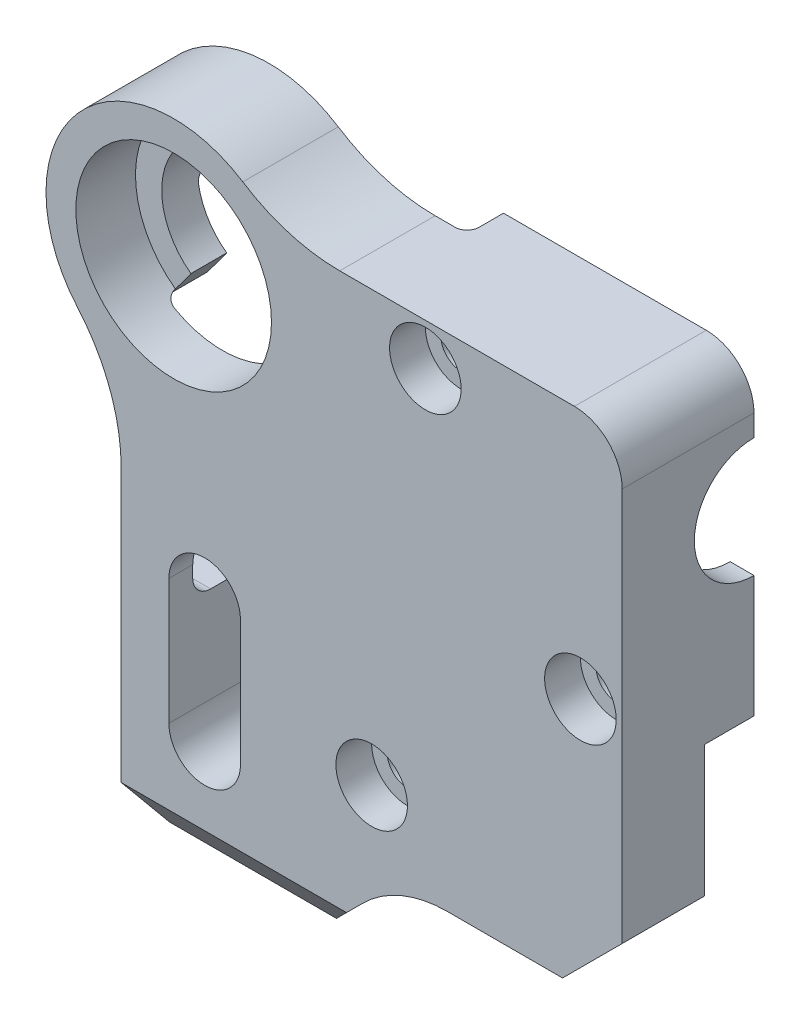
SolidWorks part; units mm, degrees
ref_plane "Plano frontal" through (0, 0, 0) normal (0, 0, 1) x (1, 0, 0)
ref_plane "Plano superior" through (0, 0, 0) normal (0, 1, 0) x (1, 0, 0)
ref_plane "Plano direito" through (0, 0, 0) normal (1, 0, 0) x (0, 0, -1)
sketch "Esboço1" plane through (0, 0, 0) normal (0, 0, 1) x (1, 0, 0)
  line L0 (0, 0) -> (-16.6, 14.4) construction
  line L1 (-21, -2.4562) -> (-21, -30.2)
  line L2 (-21, -30.2) -> (-7, -30.2)
  line L3 (-7, -30.2) -> (-0.7289, -23.9289)
  line L4 (6.3421, -21) -> (16, -21)
  line L5 (21, -16) -> (21, 17)
  line L6 (17, 21) -> (-2.6741, 21)
  line L7 (16, -21) -> (21, -16)
  line L8 (0, 0) -> (17.5, 0) construction
  line L9 (0, 0) -> (0, -15) construction
  line L10 (21, 10.2) -> (-37.1781, 10.2) construction
  line L11 (-14, -8.49) -> (-14, -19.01) construction
  line L12 (-11, -8.49) -> (-11, -19.01)
  line L13 (-17, -8.49) -> (-17, -19.01)
  arc A0 (-10.8021, 23.393) -> (-24.677, 7.3821) centre (-16.6, 14.4) ccw
  circle A1 centre (-16.6, 14.4) radius 8.2 construction
  arc A2 (21, 17) -> (17, 21) centre (17, 17) ccw
  arc A3 (-21, -2.4562) -> (-24.677, 7.3821) centre (-36, -2.4562) ccw
  arc A4 (-2.6741, 21) -> (-10.8021, 23.393) centre (-2.6741, 36) cw
  arc A5 (-0.7289, -23.9289) -> (6.3421, -21) centre (6.3421, -31) cw
  circle A7 centre (17.5, 0) radius 1.7
  circle A8 centre (0, -15) radius 1.7
  circle A9 centre (-16.6, 14.4) radius 4 construction
  circle A10 centre (4.5, 17.5) radius 1.7
  circle A11 centre (-16.6, 14.4) radius 2.7
  arc A12 (-11, -8.49) -> (-17, -8.49) centre (-14, -8.49) ccw
  arc A13 (-17, -19.01) -> (-11, -19.01) centre (-14, -19.01) ccw
  point P9 (21, -21)
  point P32 (-14, -13.75)
  dimension "D1" = 16.4
  dimension "D10" = 4
  dimension "D11" = 15
  dimension "D12" = 10
  dimension "D15" = 4
  dimension "D19" = 3.4
  dimension "D22" = 8
  dimension "D25" = 5.4
  dimension "D26" = 2.5
  dimension "D3" = 4.4
  dimension "D4" = 44.6
  dimension "D5" = 14
  dimension "D6" = 135
  dimension "D7" = 9.2
  dimension "D8" = 42
  dimension "D9" = 6.6
  dimension "D13" = 5
  dimension "D14" = 5
  dimension "D16" = 16.6
  dimension "D17" = 14.4
  dimension "D18" = 17.5
  dimension "D20" = 15
  dimension "D21" = 10.8
  dimension "D23" = 3.1
  dimension "D24" = 21.1
  dimension "D27" = 6
  dimension "D28" = 10.52
  dimension "D29" = 11.19
extrude "Ressalto-extrusão1" add sketch "Esboço1" along normal blind 14 contours L3 A5 L4 L7 L5 A2 L6 A4 A0 A3 L1 L2 A13 L13 A12 L12 A11 A10 A8 A7 region at (-1.918, -0.5242, 0)
sketch "Esboço2" plane through (0, 0, 14) normal (0, 0, -1) x (-1, 0, 0)
  circle A0 centre (-17.5, 0) radius 3
  circle A1 centre (0, -15) radius 3
  circle A2 centre (-4.5, 17.5) radius 3
  dimension "D1" = 6
extrude "Corte-extrusão1" cut sketch "Esboço2" along normal blind 3
sketch "Esboço3" plane through (-21, 0, 0) normal (-1, 0, 0) x (0, 0, 1)
  line L10 (14, -30.2) -> (14, -23.2)
  line L11 (14, -2.4562) -> (14, -30.2) construction
  line L12 (14, -23.2) -> (7, -30.2)
  line L13 (14, -30.2) -> (0, -30.2) construction
  line L14 (7, -30.2) -> (14, -30.2)
  dimension "D1" = 7
extrude "Corte-extrusão2" cut sketch "Esboço3" against normal through all
sketch "Esboço4" plane through (0, 0, 0) normal (0, 0, 1) x (1, 0, 0)
  line L10 (0, 11) -> (0, 21)
  line L22 (21, -16) -> (21, 17) construction
  line L24 (17, 21) -> (-2.6741, 21) construction
  line L25 (0, -11) -> (-11, -11)
  line L26 (-11, -8.49) -> (-11, -19.01) construction
  line L27 (-17, -8.49) -> (-17, -19.01) construction
  line L28 (-17, -8.49) -> (-17, -11)
  line L29 (-11, -8.49) -> (-11, -11)
  line L30 (-17, -11) -> (-21, -11)
  line L32 (-21, -23.2) -> (0.0843, -23.2)
  line L33 (6.3421, -21) -> (16, -21)
  line L34 (16, -21) -> (21, -16)
  line L35 (21, -16) -> (21, 17)
  line L36 (17, 21) -> (-2.6741, 21)
  line L37 (-21, -2.4562) -> (-21, -23.2)
  line L38 (-21, -23.2) -> (0.0843, -23.2)
  line L43 (0, 21) -> (-2.6741, 21)
  line L44 (-21, -2.4562) -> (-21, -11)
  circle A8 centre (0, 0) radius 5.5
  arc A9 (0, -11) -> (0, 11) centre (0, 0) ccw
  arc A19 (-11, -8.49) -> (-17, -8.49) centre (-14, -8.49) ccw construction
  arc A20 (-11, -8.49) -> (-17, -8.49) centre (-14, -8.49) ccw
  arc A24 (6.3421, -21) -> (0.0843, -23.2) centre (6.3421, -31) ccw
  arc A25 (21, 17) -> (17, 21) centre (17, 17) ccw
  arc A26 (-10.8021, 23.393) -> (-2.6741, 21) centre (-2.6741, 36) ccw
  arc A27 (-10.8021, 23.393) -> (-24.677, 7.3821) centre (-16.6, 14.4) ccw
  arc A28 (-21, -2.4562) -> (-24.677, 7.3821) centre (-36, -2.4562) ccw
  arc A31 (-10.8021, 23.393) -> (-2.6741, 21) centre (-2.6741, 36) ccw
  arc A32 (-10.8021, 23.393) -> (-24.677, 7.3821) centre (-16.6, 14.4) ccw
  arc A33 (-21, -2.4562) -> (-24.677, 7.3821) centre (-36, -2.4562) ccw
  line M87 (-11, -19.01) -> (-11, -8.49)
  arc M88 (-11, -8.49) -> (-17, -8.49) centre (-14, -8.49) ccw
  line M89 (-17, -8.49) -> (-17, -19.01)
  circle M90 centre (-16.6, 14.4) radius 2.7
  line M96 (-21, -30.2) -> (-21, -2.4562)
  arc M97 (-21, -2.4562) -> (-24.677, 7.3821) centre (-36, -2.4562) ccw
  arc M98 (-24.677, 7.3821) -> (-10.8021, 23.393) centre (-16.6, 14.4) cw
  arc M99 (-10.8021, 23.393) -> (-2.6741, 21) centre (-2.6741, 36) ccw
  line M100 (-2.6741, 21) -> (17, 21)
  dimension "D1" = 11
  dimension "D2" = 22
  dimension "D3" = 21
  dimension "D4" = 0
extrude "Corte-extrusão3" cut sketch "Esboço4" along normal blind 12 contours A9 L25 L30 L10 A8 M87 M88 M89 M96 M97 M98 M99 M100 M90 region at (-9.6685, 6.5214, 0)
sketch "Esboço5" plane through (0, 0, 0) normal (0, 0, 1) x (1, 0, 0)
  circle A1 centre (0, 0) radius 5.5
  circle A3 centre (0, 0) radius 5.5
  dimension "D1" = 0
extrude "Corte-extrusão4" cut sketch "Esboço5" along normal blind 5.55
sketch "Esboço6" plane through (0, 0, 5.55) normal (0, 0, -1) x (-1, 0, 0)
  circle A0 centre (0, 0) radius 4.3
  dimension "D1" = 8.6
extrude "Ressalto-extrusão2" add sketch "Esboço6" along normal blind 4
sketch "Esboço7" plane through (0, 0, 0) normal (0, 0, -1) x (-1, 0, 0)
  line L0 (-21, -5) -> (-9.798, -5)
  line L1 (-21, -16) -> (-21, 17) construction
  line L2 (-6.3421, -21) -> (-16, -21) construction
  line L15 (21, -30.2) -> (21, -11)
  line L16 (21, -11) -> (17, -11)
  line L17 (17, -11) -> (17, -19.01)
  line L18 (11, -19.01) -> (11, -11)
  line L19 (11, -11) -> (0, -11)
  line L20 (0, 11) -> (0, 21)
  line L21 (0, 21) -> (-17, 21)
  line L22 (-21, 17) -> (-21, -16)
  line L23 (-21, -16) -> (-16, -21)
  line L24 (-16, -21) -> (-6.3421, -21)
  line L25 (0.7289, -23.9289) -> (7, -30.2)
  line L26 (7, -30.2) -> (21, -30.2)
  line L27 (21, -30.2) -> (21, -11)
  line L28 (21, -11) -> (17, -11)
  line L29 (17, -11) -> (17, -19.01)
  line L30 (11, -19.01) -> (11, -11)
  line L31 (11, -11) -> (0, -11)
  line L34 (-21, -5) -> (-21, -16)
  line L35 (-21, -16) -> (-16, -21)
  line L36 (-16, -21) -> (-6.3421, -21)
  line L37 (0.7289, -23.9289) -> (7, -30.2)
  line L38 (7, -30.2) -> (21, -30.2)
  arc A0 (0, 11) -> (0, -11) centre (0, 0) ccw construction
  arc A5 (11, -19.01) -> (17, -19.01) centre (14, -19.01) ccw
  arc A6 (0, 11) -> (0, -11) centre (0, 0) ccw
  arc A7 (-17, 21) -> (-21, 17) centre (-17, 17) ccw
  arc A8 (0.7289, -23.9289) -> (-6.3421, -21) centre (-6.3421, -31) ccw
  arc A9 (11, -19.01) -> (17, -19.01) centre (14, -19.01) ccw
  arc A10 (-9.798, -5) -> (0, -11) centre (0, 0) ccw
  arc A12 (0.7289, -23.9289) -> (-6.3421, -21) centre (-6.3421, -31) ccw
  dimension "D1" = 16
  dimension "D2" = 0
extrude "Corte-extrusão5" cut sketch "Esboço7" against normal blind 5
sketch "Esboço8" plane through (21, 0, 0) normal (1, 0, 0) x (0, 0, -1)
  line L0 (0, -5) -> (0, 17) construction
  line L2 (-14, 21) -> (0, 21) construction
  circle A0 centre (0, 10.2) radius 6.1
  dimension "D1" = 10.8
  dimension "D2" = 12.2
extrude "Corte-extrusão6" cut sketch "Esboço8" against normal blind 10.7
sketch "Esboço9" plane through (21, 0, 0) normal (1, 0, 0) x (0, 0, -1)
  line L0 (0, 4.1) -> (0, 16.3) construction
  circle A0 centre (0, 10.2) radius 8.2
  dimension "D1" = 16.4
extrude "Corte-extrusão7" cut sketch "Esboço9" against normal blind 0.5
ref_plane "Plano1" through (15.6, 0, 0) normal (1, 0, 0) x (0, 0, -1)
sketch "Esboço10" plane through (15.6, 0, 0) normal (1, 0, 0) x (0, 0, -1)
  line L0 (0, 4.1) -> (0, 16.3) construction
  circle A0 centre (0, 10.2) radius 8.2
  arc A1 (0, 18.4) -> (0, 2) centre (0, 10.2) ccw construction
extrude "Corte-extrusão8" cut sketch "Esboço10" against normal blind 5.3
sketch "Esboço11" plane through (0, 0, 0) normal (0, 0, -1) x (-1, 0, 0)
  line L0 (0, 14.4) -> (-10.3, 14.4)
  line L1 (0, 11) -> (0, 21) construction
  line L2 (-10.3, 3.8613) -> (-10.3, 18.4) construction
  line L3 (-17, 21) -> (0, 21) construction
  line L12 (-10.3, 18.4) -> (-10.3, 3.8613)
  line L13 (0, 11) -> (0, 21)
  line L14 (0, 21) -> (-17, 21)
  line L15 (-20.747, 18.4) -> (-20.5, 18.4)
  line L16 (-20.5, 18.4) -> (-20.5, 16.3)
  line L17 (-20.5, 16.3) -> (-15.6, 16.3)
  line L18 (-15.6, 16.3) -> (-15.6, 18.4)
  line L19 (-15.6, 18.4) -> (-10.3, 18.4)
  line L20 (-10.3, 14.4) -> (-10.3, 3.8613)
  line L21 (0, 11) -> (0, 14.4)
  arc A2 (0, 11) -> (-10.3, 3.8613) centre (0, 0) ccw
  arc A3 (-17, 21) -> (-20.747, 18.4) centre (-17, 17) ccw
  arc A4 (0, 11) -> (-10.3, 3.8613) centre (0, 0) ccw
  dimension "D1" = 6.6
  dimension "D2" = 0
extrude "Corte-extrusão9" cut sketch "Esboço11" against normal blind 6.95
sketch "Esboço12" plane through (0, 0, 12) normal (0, 0, -1) x (-1, 0, 0)
  line L0 (22.6, 14.4) -> (27.3, 14.4)
  line L1 (21.7962, 17.4) -> (25.8665, 19.75)
  line L2 (16.6, 14.4) -> (18.9383, 15.75) construction
  circle A0 centre (16.6, 14.4) radius 2.7 construction
  arc A1 (24.677, 7.3821) -> (10.8021, 23.393) centre (16.6, 14.4) ccw construction
  arc A2 (27.3, 14.4) -> (25.8665, 19.75) centre (16.6, 14.4) ccw
  arc A3 (19.3, 14.4) -> (18.9383, 15.75) centre (16.6, 14.4) ccw construction
  arc A4 (22.6, 14.4) -> (21.7962, 17.4) centre (16.6, 14.4) ccw
  dimension "D2" = 6
  dimension "D1" = 30
extrude "Ressalto-extrusão3" add sketch "Esboço12" along normal blind 12
ref_plane "Plano2" through (0, 0, 3.05) normal (0, 0, -1) x (-1, 0, 0)
sketch "Esboço13" plane through (0, 0, 3.05) normal (0, 0, -1) x (-1, 0, 0)
  circle A0 centre (16.6, 14.4) radius 6
  circle A1 centre (16.6, 14.4) radius 10.7
extrude "Ressalto-extrusão4" add sketch "Esboço13" against normal up to surface (8.95 mm away) up to face at (-19.3, 14.4, 12)
sketch "Esboço14" plane through (0, 0, 14) normal (0, 0, 1) x (1, 0, 0)
  circle A0 centre (-16.6, 14.4) radius 8.2
  dimension "D1" = 16.4
extrude "Corte-extrusão10" cut sketch "Esboço14" against normal offset from surface (8.95 mm away) 2 up to face at (-16.4626, 14.3632, 3.05)
sketch "Esboço15" plane through (0, 0, 3.05) normal (0, 0, -1) x (-1, 0, 0)
  line L0 (19.0985, 11) -> (6.4546, 11)
  line L1 (2.6741, 21) -> (0, 21) construction
  line L5 (16.6, 14.4) -> (38.1394, 14.4) construction
  line L6 (19.0985, 11) -> (22.936, 5.7777)
  line L7 (19.0985, 11) -> (16.6, 14.4) construction
  arc A0 (25.8665, 19.75) -> (27.3, 14.4) centre (16.6, 14.4) ccw construction
  arc A1 (6.4546, 11) -> (22.936, 5.7777) centre (16.6, 14.4) ccw
  dimension "D1" = 10
  dimension "D2" = 53.69
extrude "Corte-extrusão11" cut sketch "Esboço15" against normal blind 3.9
sketch "Esboço16" plane through (0, 0, 3.05) normal (0, 0, -1) x (-1, 0, 0)
  line L0 (0, 11) -> (6.4546, 11)
  line L8 (2.6741, 21) -> (0, 21)
  line L9 (0, 21) -> (0, 11)
  line L10 (0, -11) -> (11, -11)
  line L11 (11, -11) -> (11, -8.49)
  line L12 (17, -8.49) -> (17, -11)
  line L13 (17, -11) -> (21, -11)
  line L14 (21, -11) -> (21, -2.4562)
  line L15 (2.6741, 21) -> (0, 21)
  line L16 (0, 21) -> (0, 11)
  arc A5 (10.8021, 23.393) -> (24.677, 7.3821) centre (16.6, 14.4) ccw
  arc A6 (2.6741, 21) -> (10.8021, 23.393) centre (2.6741, 36) ccw
  arc A7 (0, 11) -> (0, -11) centre (0, 0) ccw
  arc A8 (17, -8.49) -> (11, -8.49) centre (14, -8.49) ccw
  arc A9 (24.677, 7.3821) -> (21, -2.4562) centre (36, -2.4562) ccw
  arc A10 (10.8021, 23.393) -> (6.4546, 11) centre (16.6, 14.4) ccw
  arc A11 (2.6741, 21) -> (10.8021, 23.393) centre (2.6741, 36) ccw
  dimension "D1" = 0
extrude "Ressalto-extrusão5" add sketch "Esboço16" against normal up to surface (8.95 mm away) up to face at (-9.6009, 1.2575, 12)
sketch "Esboço17" plane through (0, 0, 5) normal (0, 0, -1) x (-1, 0, 0)
  line L11 (-21, -5) -> (-21, -16)
  line L12 (-21, -16) -> (-16, -21)
  line L13 (-16, -21) -> (-6.3421, -21)
  line L14 (0.7289, -23.9289) -> (7, -30.2)
  line L15 (7, -30.2) -> (21, -30.2)
  line L16 (21, -30.2) -> (21, -11)
  line L17 (21, -11) -> (17, -11)
  line L18 (17, -11) -> (17, -19.01)
  line L19 (11, -19.01) -> (11, -11)
  line L20 (11, -11) -> (0, -11)
  line L21 (-9.798, -5) -> (-21, -5)
  line L22 (-21, -5) -> (-21, -16)
  line L23 (-21, -16) -> (-16, -21)
  line L24 (-16, -21) -> (-6.3421, -21)
  line L25 (0.7289, -23.9289) -> (7, -30.2)
  line L26 (7, -30.2) -> (21, -30.2)
  line L27 (21, -30.2) -> (21, -11)
  line L28 (21, -11) -> (17, -11)
  line L29 (17, -11) -> (17, -19.01)
  line L30 (11, -19.01) -> (11, -11)
  line L31 (11, -11) -> (0, -11)
  line L32 (-9.798, -5) -> (-21, -5)
  circle A0 centre (0, -15) radius 1.7 construction
  circle A1 centre (0, -15) radius 1.7
  arc A3 (0.7289, -23.9289) -> (-6.3421, -21) centre (-6.3421, -31) ccw
  arc A4 (11, -19.01) -> (17, -19.01) centre (14, -19.01) ccw
  arc A5 (-9.798, -5) -> (0, -11) centre (0, 0) ccw
  arc A6 (0.7289, -23.9289) -> (-6.3421, -21) centre (-6.3421, -31) ccw
  arc A7 (11, -19.01) -> (17, -19.01) centre (14, -19.01) ccw
  arc A8 (-9.798, -5) -> (0, -11) centre (0, 0) ccw
  dimension "D1" = 0
extrude "Ressalto-extrusão6" add sketch "Esboço17" along normal blind 0.85
sketch "Esboço18" plane through (0, 0, 0) normal (0, 0, -1) x (-1, 0, 0)
  line L2 (25.8665, 19.75) -> (21.7962, 17.4)
  line L3 (22.6, 14.4) -> (27.3, 14.4)
  line L4 (25.8665, 19.75) -> (21.7962, 17.4)
  line L5 (22.6, 14.4) -> (27.3, 14.4)
  arc A2 (27.3, 14.4) -> (25.8665, 19.75) centre (16.6, 14.4) ccw
  arc A3 (22.6, 14.4) -> (21.7962, 17.4) centre (16.6, 14.4) ccw
  arc A4 (27.3, 14.4) -> (25.8665, 19.75) centre (16.6, 14.4) ccw
  arc A5 (22.6, 14.4) -> (21.7962, 17.4) centre (16.6, 14.4) ccw
  dimension "D1" = 0
extrude "Ressalto-extrusão7" add sketch "Esboço18" along normal blind 0.85
sketch "Esboço19" plane through (0, 0, 3.05) normal (0, 0, -1) x (-1, 0, 0)
  line L0 (0, 14.4) -> (10.6, 14.4)
  line L6 (0, 11) -> (11.6563, 11)
  line L7 (21.7962, 17.4) -> (25.8665, 19.75)
  line L8 (2.6741, 21) -> (0, 21)
  line L9 (0, 21) -> (0, 14.4)
  line L10 (0, 14.4) -> (0, 11)
  line L11 (0, 11) -> (11.6563, 11)
  line L15 (0, 14.4) -> (0, 11)
  arc A0 (21.7962, 17.4) -> (11.6563, 11) centre (16.6, 14.4) ccw construction
  arc A4 (21.7962, 17.4) -> (11.6563, 11) centre (16.6, 14.4) ccw
  arc A5 (25.8665, 19.75) -> (10.8021, 23.393) centre (16.6, 14.4) ccw
  arc A6 (2.6741, 21) -> (10.8021, 23.393) centre (2.6741, 36) ccw
  arc A7 (10.6, 14.4) -> (11.6563, 11) centre (16.6, 14.4) ccw
  dimension "D1" = 0
extrude "Corte-extrusão12" cut sketch "Esboço19" against normal up to surface (3.9 mm away) up to face at (-14.4734, 7.1124, 6.95)
sketch "Esboço20" plane through (0, 0, 5.05) normal (0, 0, 1) x (1, 0, 0)
  line L2 (-10.6, 14.4) -> (-8.4, 14.4)
  line L3 (-21.4557, 7.7922) -> (-20.1529, 9.5651)
  line L4 (-10.6, 14.4) -> (-8.4, 14.4)
  line L5 (-21.4557, 7.7922) -> (-20.1529, 9.5651)
  arc A2 (-10.6, 14.4) -> (-20.1529, 9.5651) centre (-16.6, 14.4) ccw
  arc A3 (-8.4, 14.4) -> (-21.4557, 7.7922) centre (-16.6, 14.4) ccw
  arc A4 (-10.6, 14.4) -> (-20.1529, 9.5651) centre (-16.6, 14.4) ccw
  arc A5 (-8.4, 14.4) -> (-21.4557, 7.7922) centre (-16.6, 14.4) ccw
  dimension "D1" = 0
extrude "Ressalto-extrusão8" add sketch "Esboço20" along normal blind 1
sketch "Esboço22" plane through (0, 0, 12) normal (0, 0, -1) x (-1, 0, 0)
  line L6 (6.4546, 11) -> (0, 11)
  line L7 (0, -11) -> (11, -11)
  line L8 (11, -11) -> (11, -8.49)
  line L9 (17, -8.49) -> (17, -11)
  line L10 (17, -11) -> (21, -11)
  line L11 (21, -11) -> (21, -2.4562)
  line L12 (6.4546, 11) -> (0, 11)
  line L13 (0, -11) -> (11, -11)
  line L14 (11, -11) -> (11, -8.49)
  line L15 (17, -8.49) -> (17, -11)
  line L16 (17, -11) -> (21, -11)
  line L17 (21, -11) -> (21, -2.4562)
  arc A4 (0, 11) -> (0, -11) centre (0, 0) ccw
  arc A5 (17, -8.49) -> (11, -8.49) centre (14, -8.49) ccw
  arc A6 (24.677, 7.3821) -> (21, -2.4562) centre (36, -2.4562) ccw
  arc A7 (6.4546, 11) -> (24.677, 7.3821) centre (16.6, 14.4) ccw
  arc A8 (0, 11) -> (0, -11) centre (0, 0) ccw
  arc A9 (17, -8.49) -> (11, -8.49) centre (14, -8.49) ccw
  arc A10 (24.677, 7.3821) -> (21, -2.4562) centre (36, -2.4562) ccw
  arc A11 (6.4546, 11) -> (24.677, 7.3821) centre (16.6, 14.4) ccw
  dimension "D1" = 0
extrude "Ressalto-extrusão9" add sketch "Esboço22" along normal blind 2.95
chamfer "Chanfro1" distance 2 angle 45 1 edges at (-22.936, 5.7777, 5)
fillet "Filete1" radius 1 5 edges at (0, 17.7, 3.05) (-23.8313, 18.575, 3.05) (-24.95, 14.4, 3.05) (-21.6037, 7.5908, 6.95) (-23.0382, 7.1927, 6.95)
sketch "Esboço21" plane through (0, 0, 14) normal (0, 0, 1) x (1, 0, 0)
  circle A0 centre (4.5, 17.5) radius 3
  circle A1 centre (0, -15) radius 3
  circle A2 centre (17.5, 0) radius 3
  circle A3 centre (4.5, 17.5) radius 3 construction
extrude "Corte-extrusão13" cut sketch "Esboço21" against normal blind 5.95
sketch "Esboço23" plane through (0, 0, 14) normal (0, 0, 1) x (1, 0, 0)
  line L1 (-31.1511, 25.3067) -> (31.1511, 25.3067)
  line L2 (-31.1511, 25.3067) -> (-31.1511, -25.3067)
  line L3 (-31.1511, -25.3067) -> (31.1511, -25.3067)
  line L4 (31.1511, 25.3067) -> (31.1511, -25.3067)
  line L5 (-31.1511, 25.3067) -> (31.1511, -25.3067) construction
  line L6 (-31.1511, -25.3067) -> (31.1511, 25.3067) construction
  point P0 (0, 0)
extrude "Corte-extrusão14" cut sketch "Esboço23" against normal blind 2.95
fillet "Filete3" radius 1.5 6 edges at (-3.2273, 11, 9.05) (-5.5, -11, 9.05) (-5.5, 0, 9.05) (-19, -11, 9.05) (-14.5163, 3.9049, 9.05) (11, 0, 9.05)
fillet "Filete4" radius 0.6 3 edges at (-17, -15.005, 4.15) (-14, -22.01, 4.15) (-11, -15.005, 4.15)
sketch "Esboço24" plane through (21, 0, 0) normal (1, 0, 0) x (0, 0, -1)
  line L0 (0, 18.4) -> (0, 15.2)
  line L1 (0, 5.2) -> (0, 2)
  arc A0 (0, 18.4) -> (0, 2) centre (0, 10.2) ccw
  arc A1 (-4.5826, 17) -> (0, 2) centre (0, 10.2) ccw construction
  arc A2 (0, 15.2) -> (0, 5.2) centre (0, 10.2) ccw
  dimension "D1" = 10
extrude "Ressalto-extrusão10" add sketch "Esboço24" against normal up to surface (10.7 mm away) up to face at (10.3, 13.7741, 4.3997)
sketch "Esboço25" plane through (0, 0, 0) normal (0, 0, -1) x (-1, 0, 0)
  line L0 (-21, 17) -> (-26.6712, 17)
  line L1 (-26.6712, 17) -> (-26.6712, 21)
  line L2 (-26.6712, 21) -> (-17, 21)
  arc A0 (-17, 21) -> (-21, 17) centre (-17, 17) ccw
  arc A1 (-17, 21) -> (-20.747, 18.4) centre (-17, 17) ccw construction
extrude "Corte-extrusão15" cut sketch "Esboço25" against normal through all both and the other way through all
ref_plane "Plano3" through (19, 0, 0) normal (1, 0, 0) x (0, 0, -1)
sketch "Esboço26" plane through (19, 0, 0) normal (1, 0, 0) x (0, 0, -1)
  line L1 (4.4456, 2.5) -> (8.8912, 10.2)
  line L2 (8.8912, 10.2) -> (4.4456, 17.9)
  line L3 (4.4456, 17.9) -> (-4.4456, 17.9)
  line L4 (-4.4456, 17.9) -> (-8.8912, 10.2)
  line L5 (-8.8912, 10.2) -> (-4.4456, 2.5)
  line L6 (-4.4456, 2.5) -> (4.4456, 2.5)
  circle A0 centre (0, 10.2) radius 7.7 construction
  dimension "D1" = 15.4
extrude "Corte-extrusão16" cut sketch "Esboço26" against normal blind 5.5
sketch "Esboço27" plane through (10.3, 0, 0) normal (1, 0, 0) x (0, 0, -1)
  circle A0 centre (0, 10.2) radius 7.7
  dimension "D1" = 15.4
extrude "Corte-extrusão17" cut sketch "Esboço27" along normal blind 1.2
sketch "Esboço28" plane through (21, 0, 0) normal (1, 0, 0) x (0, 0, -1)
  line L0 (-7, -30.2) -> (-11.05, -25.3067)
  line L1 (-11.05, -25.3067) -> (-11.8933, -25.3067)
  line L2 (-11.8933, -25.3067) -> (-11.8933, -30.2)
  line L3 (-11.8933, -30.2) -> (-7, -30.2)
extrude "Corte-extrusão18" cut sketch "Esboço28" against normal through all both and the other way through all
